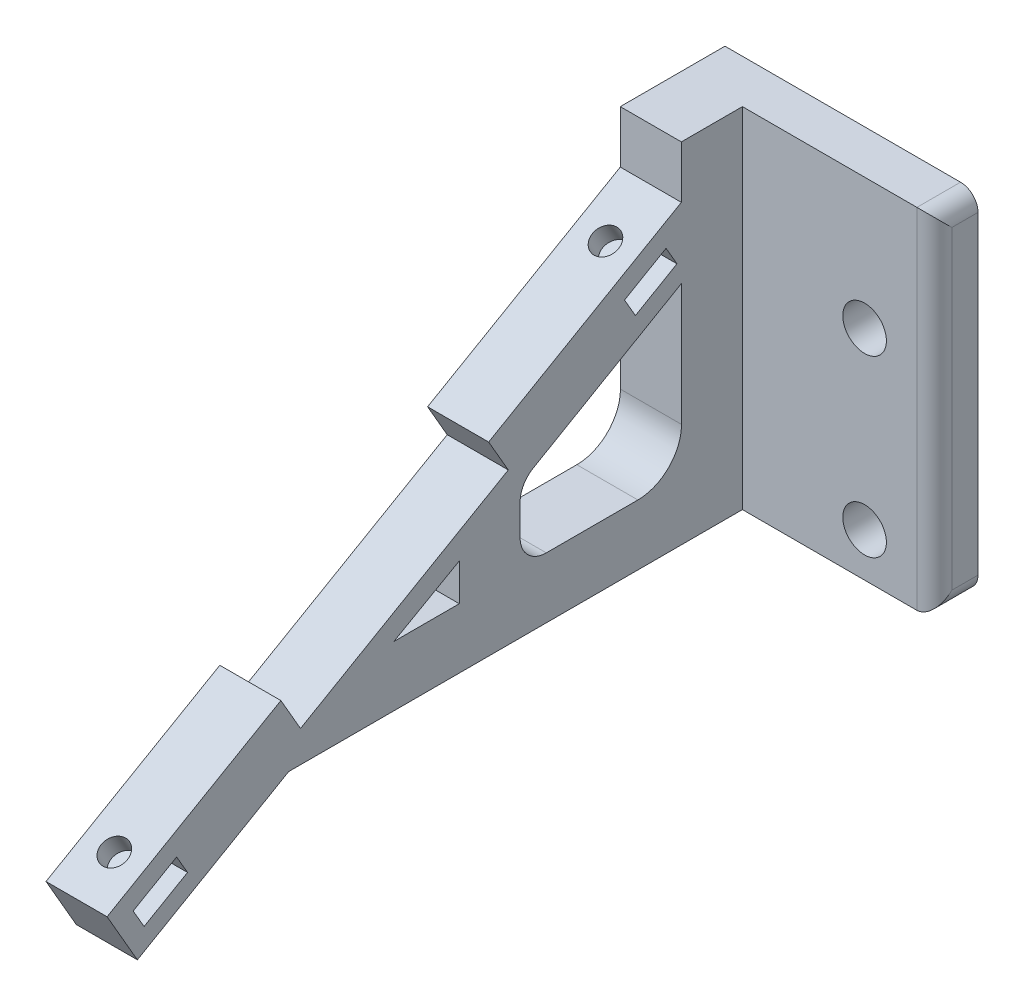
SolidWorks part; units mm, degrees
ref_plane "Front Plane" through (0, 0, 0) normal (0, 0, 1) x (1, 0, 0)
ref_plane "Top Plane" through (0, 0, 0) normal (0, 1, 0) x (1, 0, 0)
ref_plane "Right Plane" through (0, 0, 0) normal (1, 0, 0) x (0, 0, -1)
sketch "Sketch1" plane through (0, 0, 0) normal (1, 0, 0) x (0, 0, -1)
  line L0 (0, 0) -> (0, 40)
  line L1 (0, 40) -> (-7, 40)
  line L2 (-7, 40) -> (-7, 34)
  line L3 (-7, 34) -> (-29.0836, 21.25)
  line L4 (-29.0836, 21.25) -> (-26.8336, 17.3529)
  line L5 (-26.8336, 17.3529) -> (-50.6493, 3.6029)
  line L6 (-50.6493, 3.6029) -> (-52.8993, 7.5)
  line L7 (-52.8993, 7.5) -> (-72.8179, -4)
  line L8 (-72.8179, -4) -> (-69.3455, -10.0144)
  line L9 (-69.3455, -10.0144) -> (-52, 0)
  line L10 (-52, 0) -> (0, 0)
  line L11 (-69.8283, -4.9261) -> (-64.8487, -2.0511)
  line L12 (-64.8487, -2.0511) -> (-63.5987, -4.2162)
  line L13 (-63.5987, -4.2162) -> (-68.5783, -7.0912)
  line L14 (-68.5783, -7.0912) -> (-69.8283, -4.9261)
  line L15 (-39.9499, 6.884) -> (-32.4499, 11.134)
  line L16 (-32.4499, 11.134) -> (-32.4499, 6.884)
  line L17 (-32.4499, 6.884) -> (-39.9499, 6.884)
  line L18 (-6.98, 25.947) -> (-6.98, 11.947)
  line L19 (-11.98, 6.947) -> (-22.48, 6.947)
  line L20 (-25.48, 9.947) -> (-25.48, 13.5056)
  line L21 (-6.98, 25.947) -> (-23.98, 16.107)
  line L22 (-13.5125, 27.5567) -> (-8.7524, 30.3119)
  line L23 (-8.7524, 30.3119) -> (-7.5, 28.1483)
  line L24 (-7.5, 28.1483) -> (-12.2601, 25.393)
  line L25 (-12.2601, 25.393) -> (-13.5125, 27.5567)
  arc A0 (-6.98, 11.947) -> (-11.98, 6.947) centre (-11.98, 11.947) cw
  arc A1 (-22.48, 6.947) -> (-25.48, 9.947) centre (-22.48, 9.947) cw
  arc A2 (-25.48, 13.5056) -> (-23.98, 16.107) centre (-22.4743, 13.5056) cw
  dimension "D19" = 5
  dimension "D20" = 3
  dimension "D22" = 9.84
  dimension "D1" = 40
  dimension "D2" = 7
  dimension "D3" = 6
  dimension "D4" = 25.5
  dimension "D5" = 4.5
  dimension "D6" = 27.5
  dimension "D7" = 4.5
  dimension "D8" = 23
  dimension "D9" = 52
  dimension "D10" = 150
  dimension "D11" = 2.148
  dimension "D12" = 2.126
  dimension "D13" = 2.5
  dimension "D14" = 5.75
  dimension "D15" = 7.5
  dimension "D16" = 4.25
  dimension "D17" = 32.868
  dimension "D18" = 6.884
  dimension "D21" = 10.5
  dimension "D23" = 17
  dimension "D24" = 11.98
  dimension "D25" = 25.947
  dimension "D26" = 19
  dimension "D27" = 5.5
  dimension "D28" = 2.5
  dimension "D29" = 7.5
  dimension "D30" = 25.393
extrude "Boss-Extrude1" add sketch "Sketch1" against normal blind 7
sketch "Sketch2" plane through (0, 0, 0) normal (0, 0, -1) x (-1, 0, 0)
  line L0 (0, 40) -> (29, 40)
  line L1 (29, 40) -> (29, 0)
  line L2 (29, 0) -> (0, 0)
  line L3 (0, 0) -> (0, 40)
  line L4 (21, 5) -> (21, 25) construction
  circle A0 centre (21, 25) radius 2.5
  circle A1 centre (21, 5) radius 2.5
  dimension "D2" = 5
  dimension "D3" = 5
  dimension "D1" = 29
  dimension "D4" = 35
  dimension "D5" = 20
  dimension "D6" = 8
extrude "Boss-Extrude2" add sketch "Sketch2" along normal blind 5
fillet "Fillet1" radius 2 3 edges at (-29, 0, -2.5) (-29, 20, 0) (-29, 40, -2.5)
sketch "Sketch3" plane through (0, 28.5311, 16.4724) normal (0, 0.866, 0.5) x (1, 0, 0)
  line L0 (-3.5, 4.9378) -> (-3.5, -60.0622) construction
  line L1 (-7, 10.9378) -> (0, 10.9378) construction
  line L2 (0, 10.9378) -> (0, -14.5622) construction
  circle A0 centre (-3.5, 4.9378) radius 1.5
  circle A1 centre (-3.5, -60.0622) radius 1.5
  dimension "D1" = 3
  dimension "D2" = 3
  dimension "D3" = 65
  dimension "D4" = 6
  dimension "D5" = 3.5
extrude "Cut-Extrude1" cut sketch "Sketch3" against normal blind 7.5
mirror "Mirror1" about plane through (0, 0, 0) normal (1, 0, 0) of "Cut-Extrude1", "Fillet1", "Boss-Extrude2", "Boss-Extrude1"
sketch "Sketch4" plane through (0, 0, -5) normal (0, 0, -1) x (-1, 0, 0)
  line L0 (27, 40) -> (-27, 40) construction
  line L1 (0, 40) -> (36.6713, 40)
  line L2 (0, 40) -> (0, -32.4279)
  line L3 (0, -32.4279) -> (36.6713, -32.4279)
  line L4 (36.6713, 40) -> (36.6713, -32.4279)
extrude "Cut-Extrude2" cut sketch "Sketch4" against normal through all
